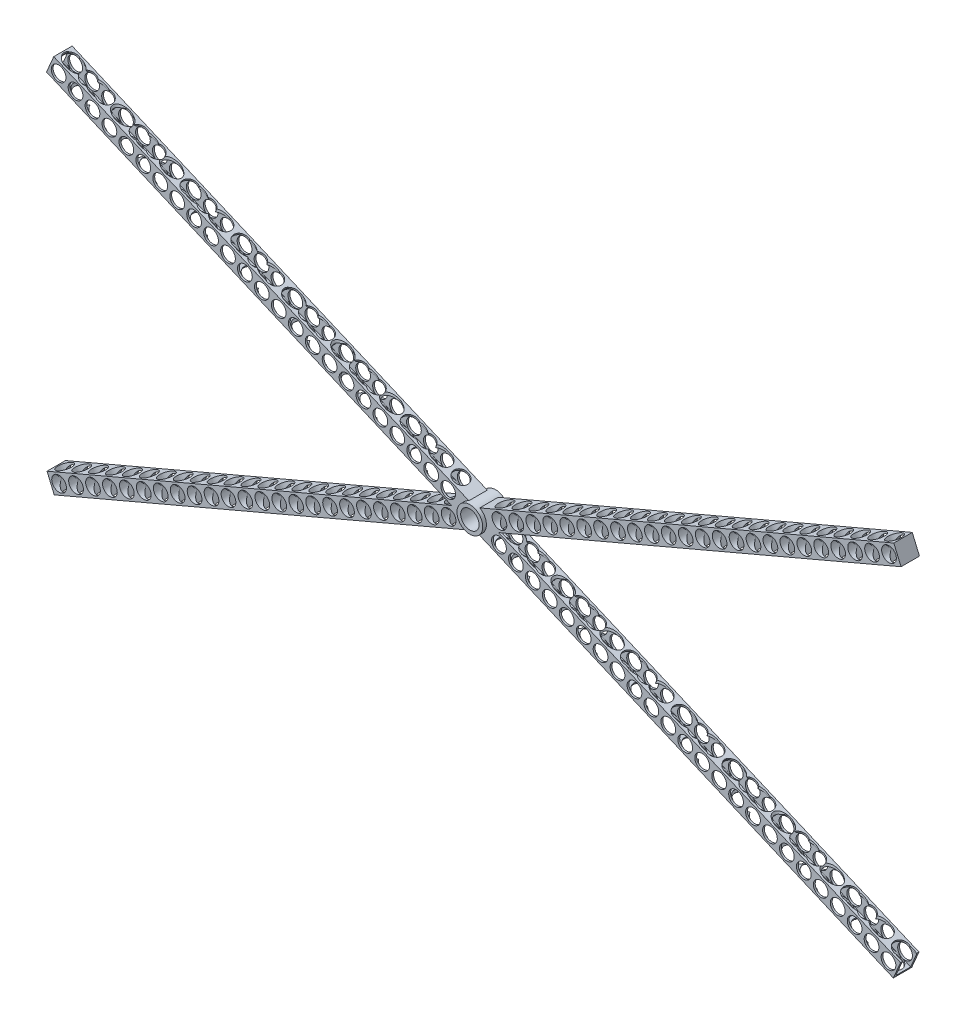
SolidWorks part; units mm, degrees
ref_plane "Ebene vorne" through (0, 0, 0) normal (0, 0, 1) x (1, 0, 0)
ref_plane "Ebene oben" through (0, 0, 0) normal (0, 1, 0) x (1, 0, 0)
ref_plane "Ebene rechts" through (0, 0, 0) normal (1, 0, 0) x (0, 0, -1)
sketch "Skizze1" plane through (0, 0, 0) normal (0, 0, 1) x (1, 0, 0)
  circle A0 centre (0, 0) radius 25
  circle A1 centre (0, 0) radius 35
  dimension "D1" = 50
  dimension "D2" = 70
extrude "Aufsatz-Linear austragen1" add sketch "Skizze1" along normal blind 70
ref_plane "Ebene1" through (0, 0, 0) normal (0.9198, 0.3923, 0) x (0, 0, -1)
ref_plane "Ebene2" through (0, 0, 0) normal (-0.9198, 0.3923, 0) x (0, 0, -1)
sketch "Skizze2" plane through (0, 0, 0) normal (0.9198, 0.3923, 0) x (0, 0, -1)
  line L1 (-60, 25) -> (-10, 25)
  line L2 (-60, 25) -> (-60, -25)
  line L3 (-60, -25) -> (-10, -25)
  line L4 (-10, 25) -> (-10, -25)
  line L5 (-60, 25) -> (-10, -25) construction
  line L6 (-60, -25) -> (-10, 25) construction
  line L7 (-70, 35) -> (-70, -35) construction
  line L8 (-70, 0) -> (0, 0) construction
  point P0 (-35, 0)
  dimension "D1" = 50
  dimension "D2" = 50
  dimension "D3" = 10
  dimension "D4" = 25
sketch "Skizze4" plane through (0, 0, 0) normal (-0.9198, 0.3923, 0) x (0, 0, -1)
  line L0 (-70, 0) -> (0, 0) construction
  line L5 (-70, 35) -> (-70, -35) construction
  line L6 (-60, 25) -> (-10, 25)
  line L7 (-60, 25) -> (-60, -25)
  line L8 (-60, -25) -> (-10, -25)
  line L9 (-10, 25) -> (-10, -25)
  line L10 (-60, 25) -> (-10, -25) construction
  line L11 (-60, -25) -> (-10, 25) construction
  point P2 (-35, 0)
  dimension "D1" = 50
  dimension "D2" = 50
  dimension "D3" = 10
extrude "Aufsatz-Linear austragen3" add sketch "Skizze4" along normal blind 1250
sketch "Skizze5" plane through (-1149.7769, 490.4214, 0) normal (-0.9198, 0.3923, 0) x (0, 0, 1)
  line L0 (70, 0) -> (0, 0) construction
  line L1 (15, 20) -> (55, 20)
  line L2 (15, 20) -> (15, -20)
  line L3 (15, -20) -> (55, -20)
  line L4 (55, 20) -> (55, -20)
  line L5 (15, 20) -> (55, -20) construction
  line L6 (15, -20) -> (55, 20) construction
  line L7 (60, 25) -> (10, 25) construction
  line L8 (10, -25) -> (60, -25) construction
  line L9 (10, 25) -> (10, -25) construction
  line L10 (60, -25) -> (60, 25) construction
  point P0 (35, 0)
  dimension "D1" = 5
  dimension "D2" = 5
  dimension "D3" = 5
  dimension "D4" = 5
extrude "Schnitt-Linear austragen2" cut sketch "Skizze5" against normal blind 1250
sketch "Skizze7" plane through (0, 0, 60) normal (0, 0, 1) x (1, 0, 0)
  line L0 (-1149.7769, 490.4214) -> (0, 0) construction
  line L1 (-1159.5853, 467.4259) -> (-1139.9684, 513.4169) construction
  circle A0 centre (-1126.7813, 480.613) radius 20
  dimension "D2" = 40
  dimension "D1" = 25
extrude "Schnitt-Linear austragen4" cut sketch "Skizze7" against normal through all both and the other way through all
pattern_linear "Lineares Muster2" count 24 spacing 50 along (0.9198, -0.3923, 0) of "Schnitt-Linear austragen4"
sketch "Skizze9" plane through (-9.8084, -22.9955, 0) normal (-0.3923, -0.9198, 0) x (0.9198, -0.3923, 0)
  line L0 (-1250, 35) -> (15.8966, 35) construction
  line L1 (-1250, 10) -> (-1250, 60) construction
  circle A0 centre (-1225, 35) radius 20
  dimension "D1" = 40
  dimension "D2" = 25
extrude "Schnitt-Linear austragen6" cut sketch "Skizze9" against normal through all both and the other way through all
pattern_linear "Lineares Muster3" count 24 spacing 50 along (0.9198, -0.3923, 0) of "Schnitt-Linear austragen6"
sketch "Skizze10" plane through (0, 0, 0) normal (0, 0, -1) x (-1, 0, 0)
  circle A0 centre (0, 0) radius 25
mirror "Spiegeln7" about plane through (0, 0, 0) normal (-0.9198, 0.3923, 0) of "Lineares Muster3", "Schnitt-Linear austragen6", "Lineares Muster2", "Schnitt-Linear austragen4", "Schnitt-Linear austragen2", "Aufsatz-Linear austragen3"
sketch "Skizze11" plane through (0, 0, 0) normal (0.9198, 0.3923, 0) x (0, 0, -1)
  line L0 (-35, 884.8967) -> (-35, -28.7771) construction
  line L1 (-60, 21.5292) -> (-10, 21.5292)
  line L2 (-60, 21.5292) -> (-60, -28.4708)
  line L3 (-60, -28.4708) -> (-10, -28.4708)
  line L4 (-10, 21.5292) -> (-10, -28.4708)
  line L5 (-60, 21.5292) -> (-10, -28.4708) construction
  line L6 (-60, -28.4708) -> (-10, 21.5292) construction
  line L7 (-70, 35) -> (-70, -35) construction
  point P0 (-35, -3.4708)
  dimension "D1" = 50
  dimension "D2" = 50
  dimension "D3" = 10
extrude "Aufsatz-Linear austragen4" add sketch "Skizze11" along normal blind 1250
sketch "Skizze12" plane through (0, 0, 60) normal (0, 0, 1) x (1, 0, 0)
  line L0 (1151.1386, 487.2288) -> (0, 0) construction
  line L1 (1141.3302, 510.2244) -> (1160.947, 464.2333) construction
  circle A0 centre (1128.1158, 477.4843) radius 20
  dimension "D1" = 40
  dimension "D2" = 25
extrude "Schnitt-Linear austragen8" cut sketch "Skizze12" against normal through all both and the other way through all
pattern_linear "Lineares Muster4" count 24 spacing 50 along (-0.9198, -0.3923, 0) of "Schnitt-Linear austragen8"
sketch "Skizze13" plane through (-8.4467, 19.803, 0) normal (-0.3923, 0.9198, 0) x (0.9198, 0.3923, 0)
  line L0 (1250, -35) -> (27.5952, -35) construction
  line L1 (1250, -10) -> (1250, -60) construction
  line L2 (27.5952, -10) -> (27.5952, -60) construction
  circle A0 centre (1225, -35) radius 20
  dimension "D1" = 40
  dimension "D2" = 25
extrude "Schnitt-Linear austragen9" cut sketch "Skizze13" against normal through all both and the other way through all
pattern_linear "Lineares Muster5" count 24 spacing 50 along (-0.9198, -0.3923, 0) of "Schnitt-Linear austragen9"
mirror "Spiegeln8" about plane through (0, 0, 0) normal (0.9198, 0.3923, 0) of "Lineares Muster5", "Schnitt-Linear austragen9", "Lineares Muster4", "Schnitt-Linear austragen8", "Aufsatz-Linear austragen4"
sketch "Skizze14" plane through (0, 0, 0) normal (0, 0, -1) x (-1, 0, 0)
  circle A0 centre (0, 0) radius 25
extrude "Schnitt-Linear austragen10" cut sketch "Skizze14" against normal through all
